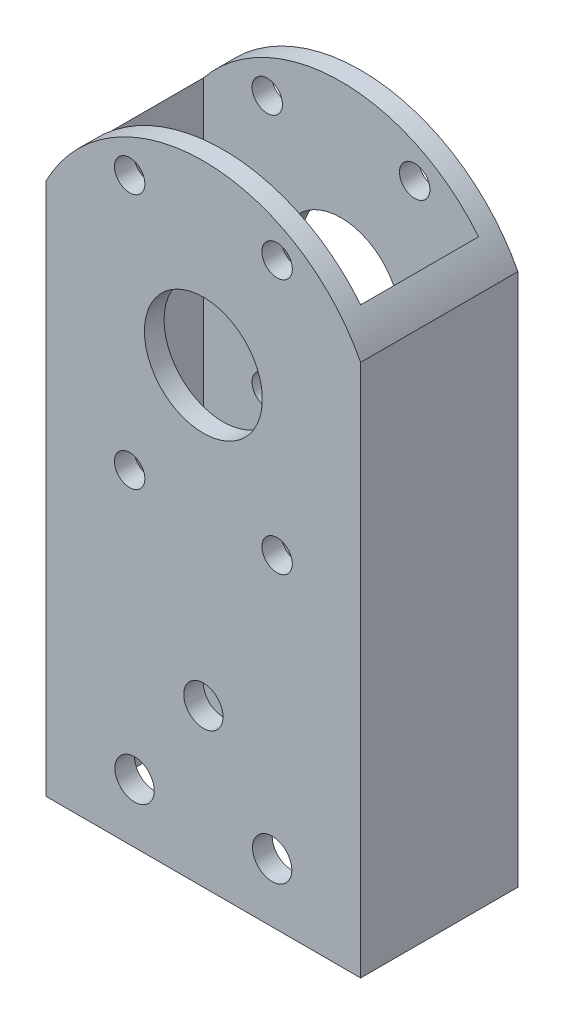
SolidWorks part; units mm, degrees
material "6061-T6 (SS)"
ref_plane "Front" through (0, 0, 0) normal (0, 0, 1) x (1, 0, 0)
ref_plane "Top" through (0, 0, 0) normal (0, 1, 0) x (1, 0, 0)
ref_plane "Right" through (0, 0, 0) normal (1, 0, 0) x (0, 0, -1)
sketch "Sketch1" plane through (0, 0, 0) normal (0, 1, 0) x (1, 0, 0)
  line L1 (-25.4, -12.7) -> (25.4, -12.7)
  line L2 (-25.4, -12.7) -> (-25.4, 12.7)
  line L3 (-25.4, 12.7) -> (25.4, 12.7)
  line L4 (25.4, -12.7) -> (25.4, 12.7)
  line L5 (-25.4, -12.7) -> (25.4, 12.7) construction
  line L6 (-25.4, 12.7) -> (25.4, -12.7) construction
  point P0 (0, 0)
  dimension "D1" = 25.4
  dimension "D2" = 50.8
extrude "Extrude-Thin1" add sketch "Sketch1" along normal blind 101.6 thin thin type one direction reverse wall 3.175
sketch "Sketch2" plane through (0, 0, -12.7) normal (0, 0, -1) x (-1, 0, 0)
  line L0 (0, 101.6) -> (0, 69.85)
  line L1 (-25.4, 101.6) -> (25.4, 101.6) construction
  line L3 (0, 60.325) -> (0, 79.375) construction
  circle A1 centre (0, 69.85) radius 23.8125
  circle A3 centre (0, 69.85) radius 9.525
  point P12 (0, 69.85)
  dimension "D1" = 19.05
  dimension "D3" = 47.625
  dimension "D2" = 31.75
hole_wizard "#10 (0.1935) Diameter Hole2" positions "Sketch5" profile "Sketch6" hole size "#10" standard "ANSI Inch" end condition through all
sketch "Sketch5" plane through (0, 0, -12.7) normal (0, 0, -1) x (-1, 0, 0)
  line L0 (0, 101.6) -> (0, 73.025)
  line L1 (-25.4, 101.6) -> (25.4, 101.6) construction
  line L3 (-11.9063, 93.6472) -> (11.9063, 93.6472)
  line L4 (-11.9063, 93.6472) -> (-11.9063, 52.4028)
  line L5 (-11.9063, 52.4028) -> (11.9063, 52.4028)
  line L6 (11.9063, 93.6472) -> (11.9063, 52.4028)
  circle A0 centre (0, 73.025) radius 23.8125
  point P21 (-11.9063, 93.6472)
  point P22 (11.9063, 93.6472)
  point P24 (11.9063, 52.4028)
  point P25 (-11.9063, 52.4028)
  dimension "D1" = 47.625
  dimension "D2" = 28.575
  dimension "D3" = 23.8125
sketch "Sketch6" plane through (11.9063, 52.4028, -12.7) normal (1, 0, 0) x (0, 1, 0)
  line L0 (0, 0) -> (0, 25.4)
  line L1 (0, 25.4) -> (2.4574, 25.4)
  line L2 (2.4574, 25.4) -> (2.4574, 0)
  line L5 (2.4574, 0) -> (0, 0)
  line L11 (0, -6.35) -> (0, 107.95) construction
  dimension "Thru Hole Dia." = 4.9149
  dimension "Thru Hole Depth" = 25.4
sketch "Sketch7" plane through (0, 0, -12.7) normal (0, 0, -1) x (-1, 0, 0)
  line L0 (-11.9063, 93.6472) -> (11.9063, 52.4028) construction
  circle A1 centre (0, 73.025) radius 9.525
  point P9 (0, 73.025)
  dimension "D1" = 19.05
extrude "Cut-Extrude2" cut sketch "Sketch7" against normal through all both
hole_wizard "1/4 (0.25) Diameter Hole1" positions "Sketch8" profile "Sketch9" hole size "1/4" standard "ANSI Inch" end condition through all
sketch "Sketch8" plane through (0, 0, 12.7) normal (0, 0, 1) x (1, 0, 0)
  line L2 (-25.4, 101.6) -> (-25.4, 0) construction
  line L4 (-25.4, 0) -> (25.4, 0) construction
  point P0 (-11.1125, 9.525)
  point P2 (11.1125, 9.525)
  point P14 (-109.1715, 68.7854)
  dimension "D1" = 22.225
  dimension "D2" = 14.2875
  dimension "D3" = 9.525
sketch "Sketch9" plane through (-11.1125, 9.525, 12.7) normal (1, 0, 0) x (0, -1, 0)
  line L0 (0, 0) -> (0, 25.4)
  line L1 (0, 25.4) -> (3.175, 25.4)
  line L2 (3.175, 25.4) -> (3.175, 0)
  line L5 (3.175, 0) -> (0, 0)
  line L11 (0, -6.35) -> (0, 107.95) construction
  dimension "Thru Hole Dia." = 6.35
  dimension "Thru Hole Depth" = 25.4
sketch "Sketch10" plane through (0, 0, -12.7) normal (0, 0, -1) x (-1, 0, 0)
  line L0 (-25.4, 86.1159) -> (-25.4, 101.6)
  line L1 (-25.4, 101.6) -> (25.4, 101.6)
  line L2 (25.4, 101.6) -> (25.4, 86.1159)
  line L3 (25.4, 101.6) -> (25.4, 0) construction
  arc A0 (25.4, 86.1159) -> (-25.4, 86.1159) centre (0, 73.025) ccw
  line M13 (25.4, 0) -> (25.4, 101.6)
  line M14 (25.4, 101.6) -> (-25.4, 101.6)
  line M15 (-25.4, 101.6) -> (-25.4, 0)
extrude "Cut-Extrude3" cut sketch "Sketch10" against normal through all contours A0 L1 M15 | A0 M13 M14 region at (-19.4433, 97.2944, -12.7) region at (19.4433, 97.2944, -12.7)
sketch "Sketch13" plane through (0, 0, 12.7) normal (0, 0, 1) x (1, 0, 0)
  line L4 (-25.4, 86.1159) -> (-25.4, 0) construction
  point P0 (0, 25.4)
  point P10 (-61.3588, -54.1264)
  dimension "D1" = 25.4
  dimension "D2" = 25.4
hole_wizard "1/4 (0.25) Diameter Hole2" positions "Sketch13" profile "Sketch12" hole size "1/4" standard "ANSI Inch" end condition through all
sketch "Sketch12" plane through (0, 25.4, 12.7) normal (1, 0, 0) x (0, -1, 0)
  line L0 (0, 0) -> (0, 25.4)
  line L1 (0, 25.4) -> (3.175, 25.4)
  line L2 (3.175, 25.4) -> (3.175, 0)
  line L5 (3.175, 0) -> (0, 0)
  line L11 (0, -6.35) -> (0, 107.95) construction
  dimension "Thru Hole Dia." = 6.35
  dimension "Thru Hole Depth" = 25.4
